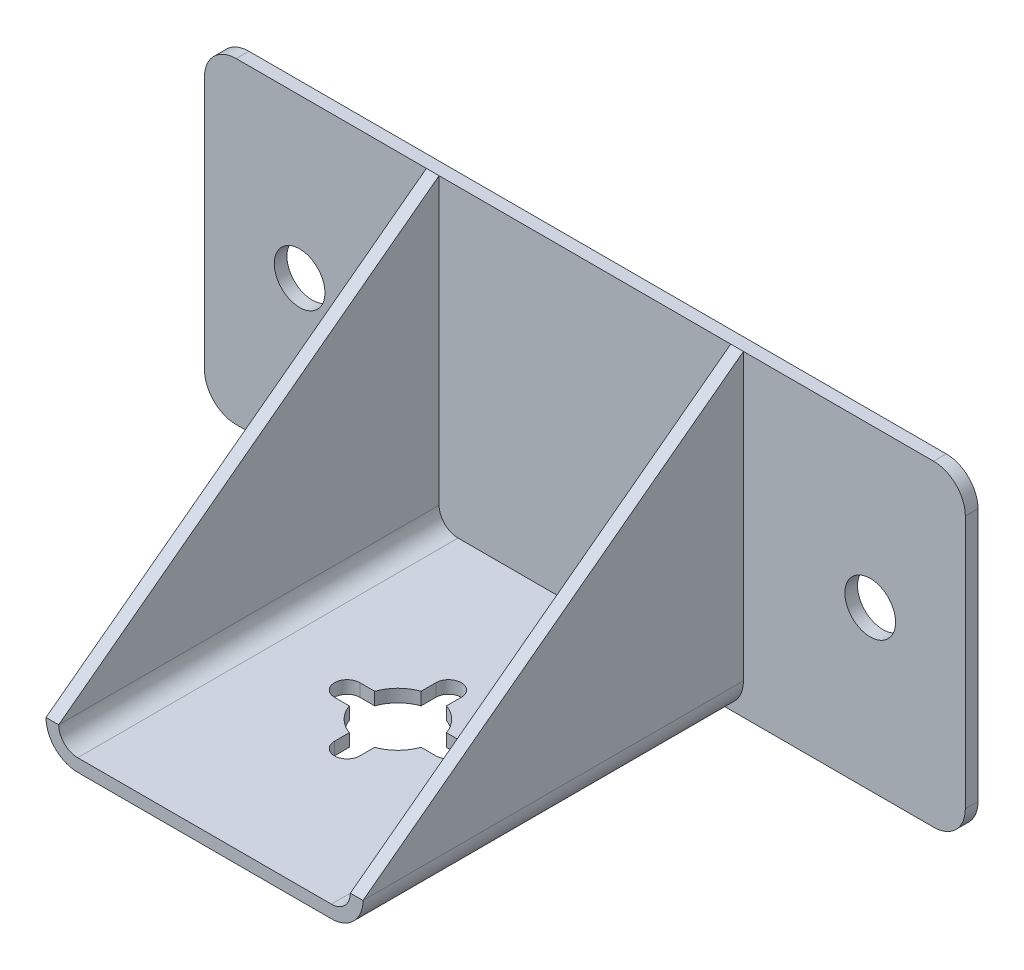
SolidWorks part; units mm, degrees
material "AISI 1020"
ref_plane "Alzado" through (0, 0, 0) normal (0, 0, 1) x (1, 0, 0)
ref_plane "Planta" through (0, 0, 0) normal (0, 1, 0) x (1, 0, 0)
ref_plane "Vista lateral" through (0, 0, 0) normal (1, 0, 0) x (0, 0, -1)
sketch "Croquis1" plane through (0, 0, 0) normal (0, 0, 1) x (1, 0, 0)
  line L1 (-55, -25) -> (55, -25)
  line L2 (-60, -20) -> (-60, 20)
  line L3 (-55, 25) -> (55, 25)
  line L4 (60, -20) -> (60, 20)
  line L5 (-60, -25) -> (60, 25) construction
  line L6 (-60, 25) -> (60, -25) construction
  arc A0 (55, 25) -> (60, 20) centre (55, 20) cw
  arc A1 (55, -25) -> (60, -20) centre (55, -20) ccw
  arc A2 (-55, -25) -> (-60, -20) centre (-55, -20) cw
  arc A3 (-60, 20) -> (-55, 25) centre (-55, 20) cw
  point P0 (0, 0)
  dimension "D3" = 5
  dimension "D1" = 120
  dimension "D2" = 50
extrude "Saliente-Extruir1" add sketch "Croquis1" along normal blind 2
sketch "Croquis2" plane through (0, 0, 2) normal (0, 0, 1) x (1, 0, 0)
  line L0 (55, 25) -> (-55, 25) construction
  line L1 (-20, -25) -> (20, -25)
  line L2 (-25, -20) -> (-25, 25)
  line L3 (-25, 25) -> (25, 25) construction
  line L4 (25, -20) -> (25, 25)
  line L5 (-25, -25) -> (25, 25) construction
  line L6 (-25, 25) -> (25, -25) construction
  line L7 (23, -20) -> (23, 25)
  line L8 (-20, -23) -> (20, -23)
  line L9 (-23, -20) -> (-23, 25)
  line L10 (-25, 25) -> (-23, 25)
  line L11 (23, 25) -> (25, 25)
  arc A0 (20, -25) -> (25, -20) centre (20, -20) ccw
  arc A1 (-20, -25) -> (-25, -20) centre (-20, -20) cw
  arc A2 (20, -23) -> (23, -20) centre (20, -20) ccw
  arc A3 (-20, -23) -> (-23, -20) centre (-20, -20) cw
  point P0 (0, 0)
  dimension "D2" = 5
  dimension "D1" = 50
  dimension "D3" = 2
extrude "Saliente-Extruir2" add sketch "Croquis2" along normal blind 60
sketch "Croquis3" plane through (25, 0, 0) normal (1, 0, 0) x (0, 0, -1)
  line L0 (-62, -20) -> (-2, 25)
  line L4 (-2, -20) -> (-2, 25)
  line L5 (-2, 25) -> (-62, 25)
  line L6 (-62, 25) -> (-62, -20)
  line L7 (-62, -20) -> (-2, -20)
  line L8 (-2, -20) -> (-2, 25)
  line L9 (-2, 25) -> (-62, 25)
  line L10 (-62, 25) -> (-62, -20)
  line L11 (-62, -20) -> (-2, -20)
  line M6 (-2, 25) -> (-62, 25)
  line M7 (-62, 25) -> (-62, -20)
  dimension "D1" = 0
extrude "Cortar-Extruir1" cut sketch "Croquis3" against normal up to surface (50 mm away) contours L0 M7 M6 region at (25, 10, 42) up to face at (-25, 2.5, 32)
sketch "Croquis4" plane through (0, 0, 0) normal (0, 0, -1) x (-1, 0, 0)
  line L0 (-45, 0) -> (45, 0) construction
  circle A0 centre (-45, 0) radius 4
  circle A1 centre (45, 0) radius 4
  point P4 (0, 0)
  dimension "D1" = 8
  dimension "D2" = 90
extrude "Cortar-Extruir2" cut sketch "Croquis4" against normal up to surface (2 mm away) up to face at (43.3009, -3.0051, 2)
sketch "Croquis5" plane through (0, -25, 0) normal (0, -1, 0) x (1, 0, 0)
  line L0 (0, 31.5) -> (0, 23.5) construction
  line L1 (2, 23.5) -> (2, 25.8431)
  line L2 (-2, 23.5) -> (-2, 25.8431)
  line L3 (-8, 29.5) -> (-5.6569, 29.5)
  line L4 (-8, 33.5) -> (-5.6569, 33.5)
  line L5 (-2, 39.5) -> (-2, 37.1569)
  line L6 (2, 39.5) -> (2, 37.1569)
  line L7 (8, 33.5) -> (5.6569, 33.5)
  line L8 (8, 29.5) -> (5.6569, 29.5)
  circle A0 centre (0, 31.5) radius 6 construction
  circle A1 centre (0, 31.5) radius 6
  circle A2 centre (0, 23.5) radius 2
  circle A3 centre (-8, 31.5) radius 2
  circle A4 centre (0, 39.5) radius 2
  circle A5 centre (8, 31.5) radius 2
  point P14 (0, 31.5)
  point P31 (0, 31.5)
  dimension "D1" = 4
  dimension "D2" = 8
  dimension "D3" = 4
  dimension "D4" = 4
extrude "Cortar-Extruir6" cut sketch "Croquis5" against normal up to surface (2 mm away) contours A1 | A5 | A4 | A3 | A4 L5 A1 | A4 A1 L6 | A5 L7 A1 | A2 L1 A1 | A2 A1 L2 | A2 | A5 A1 L8 | A3 L3 A1 | A3 A1 L4 region at (1.5428, -25, 25.1677) region at (0, -25, 23.5) region at (0, -25, 31.5) region at (-1.5428, -25, 25.1677) region at (6.3323, -25, 29.9572) region at (8, -25, 31.5) region at (6.3323, -25, 33.0428) region at (-6.3323, -25, 29.9572) region at (-8, -25, 31.5) region at (-6.3323, -25, 33.0428) region at (1.5428, -25, 37.8323) region at (0, -25, 39.5) region at (-1.5428, -25, 37.8323) up to face at (0, -23, 32)
